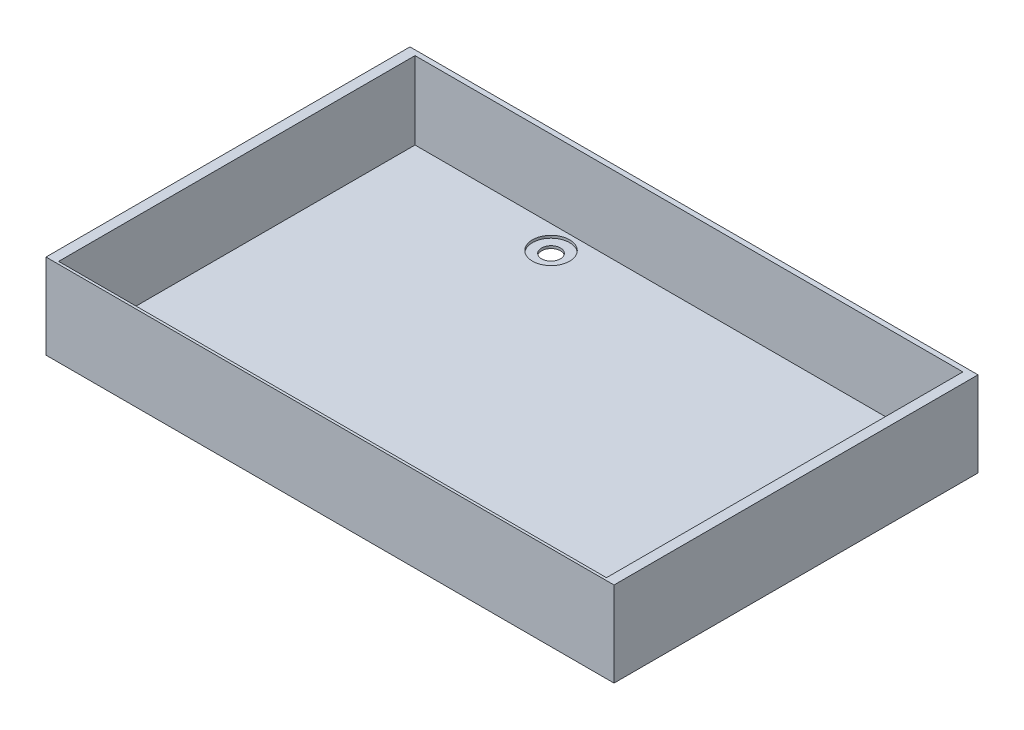
SolidWorks part; units mm, degrees
ref_plane "Ebene vorne" through (0, 0, 0) normal (0, 0, 1) x (1, 0, 0)
ref_plane "Ebene oben" through (0, 0, 0) normal (0, 1, 0) x (1, 0, 0)
ref_plane "Ebene rechts" through (0, 0, 0) normal (1, 0, 0) x (0, 0, -1)
ref_plane "Ebene1" through (0, -1.2, 0) normal (0, 1, 0) x (1, 0, 0)
sketch "Skizze1" plane through (0, 0, 0) normal (0, 1, 0) x (1, 0, 0)
  line L0 (-55, 0) -> (55, 0) construction
  line L1 (0, 0) -> (90.2, 0)
  line L2 (0, 0) -> (0, 57.8)
  line L3 (0, 57.8) -> (90.2, 57.8)
  line L4 (90.2, 0) -> (90.2, 57.8)
  line L5 (0, -55) -> (0, 55) construction
  line L7 (1.6, 0.4) -> (88.6, 0.4)
  line L8 (1.6, 0.4) -> (1.6, 57)
  line L9 (1.6, 57) -> (88.6, 57)
  line L10 (88.6, 0.4) -> (88.6, 57)
  dimension "D1" = 90.2
  dimension "D2" = 57.8
  dimension "D3" = 0.8
  dimension "D4" = 1.6
  dimension "D5" = 0.4
  dimension "D6" = 1.6
extrude "Aufsatz-Linear austragen1" add sketch "Skizze1" along normal blind 12.3
sketch "Skizze2" plane through (0, 0, 0) normal (0, 1, 0) x (1, 0, 0)
  line L0 (0, -6.765) -> (0, 6.765) construction
  line L1 (0, 0) -> (90.2, 0)
  line L2 (0, 0) -> (0, 57.8)
  line L3 (0, 57.8) -> (90.2, 57.8)
  line L4 (90.2, 0) -> (90.2, 57.8)
  line L5 (-6.765, 0) -> (6.765, 0) construction
  dimension "D1" = 57.8
  dimension "D2" = 90.2
extrude "Aufsatz-Linear austragen2" add sketch "Skizze2" against normal up to surface (1.2 mm away) up to plane "Ebene1"
ref_axis "Achse1" through (84.9, 61.5012, -53.3) along (0, -1, 0)
ref_axis "Achse2" through (26.9, 61.5012, -53.3) along (0, -1, 0)
ref_axis "Achse3" through (84.9, 54.2543, -4.3) along (0, -1, 0)
ref_axis "Achse4" through (26.9, 41.9945, -4.3) along (0, -1, 0)
sketch "Skizze3" plane through (0, 0, 0) normal (0, 1, 0) x (1, 0, 0)
  circle A0 centre (84.9, 53.3) radius 1.5
  circle A1 centre (26.9, 53.3) radius 1.5
  circle A2 centre (84.9, 4.3) radius 1.5
  circle A3 centre (26.9, 4.3) radius 1.5
  point P8 (0, 0)
  point P10 (0, 0)
  point P12 (0, 0)
  dimension "D1" = 3
extrude "Schnitt-Linear austragen1" cut sketch "Skizze3" against normal blind 1.2
sketch "Skizze4" plane through (0, -1.2, 0) normal (0, 1, 0) x (1, 0, 0)
  circle A0 centre (84.9, 53.3) radius 2.45
  circle A1 centre (26.9, 53.3) radius 2.45
  circle A2 centre (84.9, 4.3) radius 2.45
  circle A3 centre (26.9, 4.3) radius 2.45
  point P8 (0, 0)
  point P10 (0, 0)
  point P12 (0, 0)
  point P14 (0, 0)
  dimension "D1" = 4.9
extrude "Schnitt-Linear austragen2" cut sketch "Skizze4" along normal blind 0.4
sketch "Skizze5" plane through (0, 0, 0) normal (0, 1, 0) x (1, 0, 0)
  circle A0 centre (84.9, 53.3) radius 2.95
  circle A1 centre (26.9, 53.3) radius 2.95
  circle A2 centre (84.9, 4.3) radius 2.95
  circle A3 centre (26.9, 4.3) radius 2.95
  point P8 (0, 0)
  point P10 (0, 0)
  point P12 (0, 0)
  dimension "D1" = 5.9
extrude "Schnitt-Linear austragen3" cut sketch "Skizze5" against normal blind 0.4
